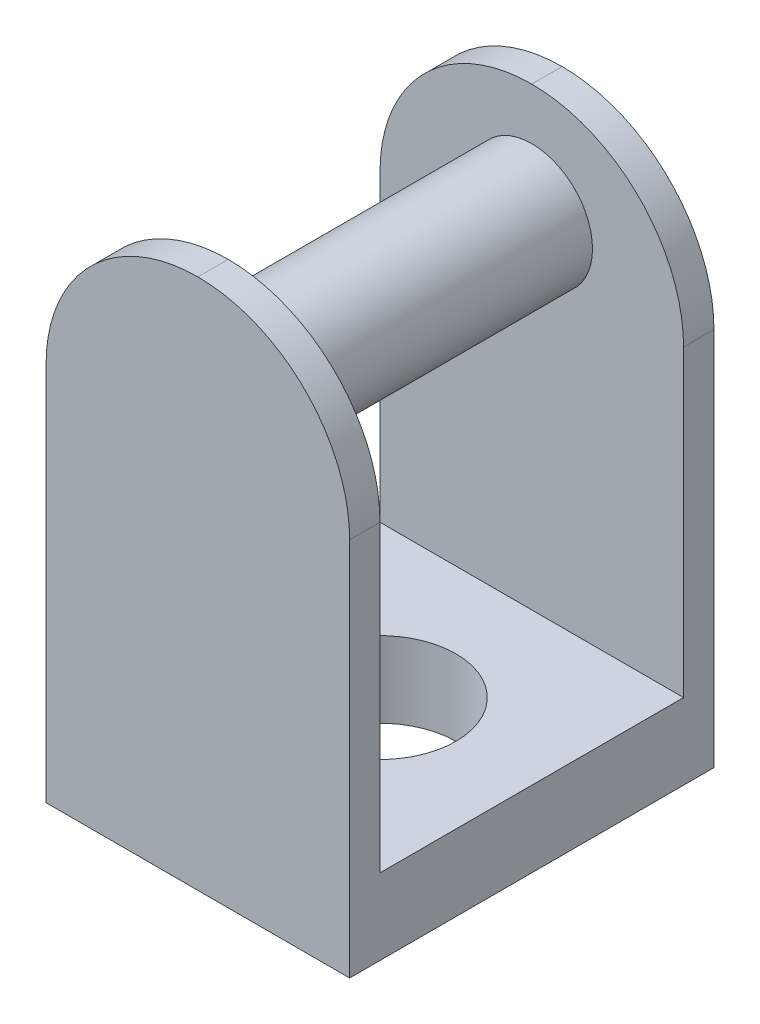
SolidWorks part; units mm, degrees
ref_plane "Front Plane" through (0, 0, 0) normal (0, 0, 1) x (1, 0, 0)
ref_plane "Top Plane" through (0, 0, 0) normal (0, 1, 0) x (1, 0, 0)
ref_plane "Right Plane" through (0, 0, 0) normal (1, 0, 0) x (0, 0, -1)
sketch "Sketch1" plane through (0, 0, 0) normal (0, 1, 0) x (1, 0, 0)
  line L1 (-10, 10) -> (10, 10)
  line L2 (-10, 10) -> (-10, -10)
  line L3 (-10, -10) -> (10, -10)
  line L4 (10, 10) -> (10, -10)
  line L5 (-10, 10) -> (10, -10) construction
  line L6 (-10, -10) -> (10, 10) construction
  circle A0 centre (0, 0) radius 5
extrude "Boss-Extrude1" add sketch "Sketch1" along normal blind 5
sketch "Sketch2" plane through (0, 5, 0) normal (0, 1, 0) x (1, 0, 0)
  line L4 (-10, -10) -> (10, -10)
  line L5 (-10, -10) -> (-10, -12)
  line L6 (10, -10) -> (10, -12)
  line L7 (-10, -12) -> (10, -12)
  line L8 (10, 10) -> (-10, 10)
  line L9 (10, 10) -> (10, 12)
  line L10 (-10, 10) -> (-10, 12)
  line L11 (10, 12) -> (-10, 12)
extrude "Boss-Extrude2" add sketch "Sketch2" against normal up to surface (5 mm away) and the other way blind 30 up to face at (0, 0, 0)
fillet "Fillet1" radius 10 4 edges at (10, 35, -11) (10, 35, 11) (-10, 35, 11) (-10, 35, -11)
sketch "Sketch4" plane through (0, 0, 10) normal (0, 0, -1) x (-1, 0, 0)
  line L0 (10, 5) -> (-10, 5) construction
  line L1 (-10, 5) -> (0, 5) construction
  line L2 (0, 5) -> (0, 27.6041) construction
  circle A0 centre (0, 27.6041) radius 4
extrude "Boss-Extrude4" add sketch "Sketch4" along normal up to surface (20 mm away) up to face at (2, 23.8284, -10)
